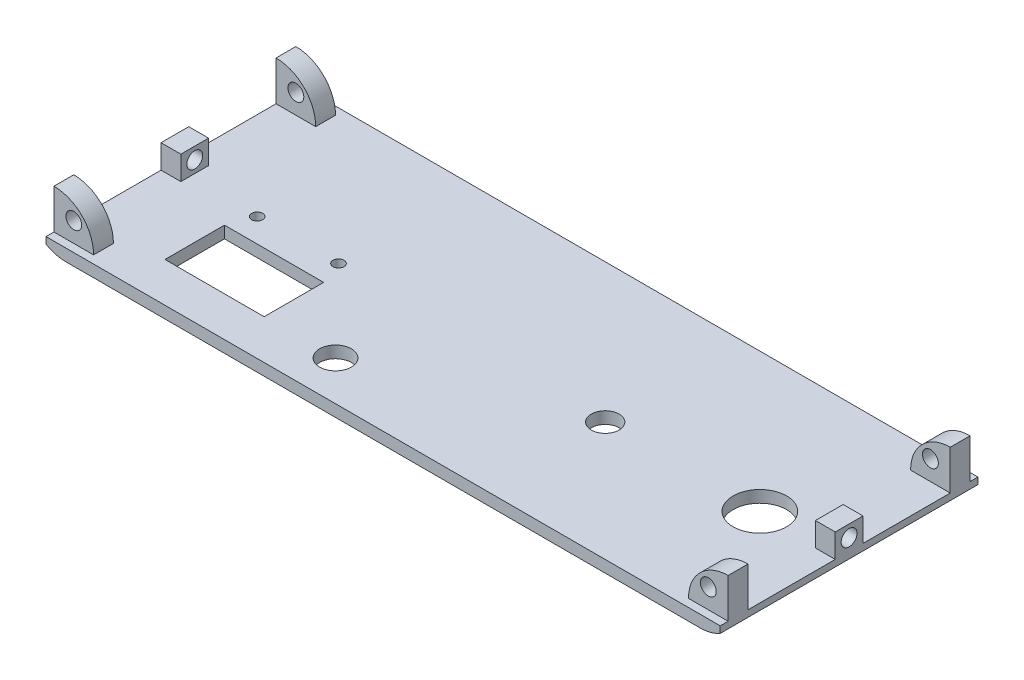
SolidWorks part; units mm, degrees
material "Allzweck-PBT"
ref_plane "Ebene vorne" through (0, 0, 0) normal (0, 0, 1) x (1, 0, 0)
ref_plane "Ebene oben" through (0, 0, 0) normal (0, 1, 0) x (1, 0, 0)
ref_plane "Ebene rechts" through (0, 0, 0) normal (1, 0, 0) x (0, 0, -1)
sketch "Skizze1" plane through (0, 0, 0) normal (0, 1, 0) x (1, 0, 0)
  line L1 (-90, 32.5) -> (90, 32.5)
  line L2 (-90, 32.5) -> (-90, -32.5)
  line L3 (-90, -32.5) -> (90, -32.5)
  line L4 (90, 32.5) -> (90, -32.5)
  line L5 (-90, 32.5) -> (90, -32.5) construction
  line L6 (-90, -32.5) -> (90, 32.5) construction
  point P0 (0, 0)
  dimension "D1" = 180
  dimension "D2" = 65
extrude "Aufsatz-Linear austragen1" add sketch "Skizze1" along normal blind 3
sketch "Skizze2" plane through (0, 0, 0) normal (0, -1, 0) x (-1, 0, 0)
  line L0 (90, 32.5) -> (90, -32.5) construction
  line L1 (65, -22.5) -> (40, -22.5)
  line L2 (65, -22.5) -> (65, -7.5)
  line L3 (65, -7.5) -> (40, -7.5)
  line L4 (40, -22.5) -> (40, -7.5)
  line L5 (65, -22.5) -> (40, -7.5) construction
  line L6 (65, -7.5) -> (40, -22.5) construction
  line L7 (-90, 32.5) -> (90, 32.5) construction
  point P0 (52.5, -15)
  dimension "D1" = 25
  dimension "D2" = 15
  dimension "D3" = 25
  dimension "D4" = 40
extrude "Schnitt-Linear austragen1" cut sketch "Skizze2" against normal blind 3
sketch "Skizze3" plane through (0, 3, 0) normal (0, 1, 0) x (1, 0, 0)
  line L0 (-90, 32.5) -> (-90, -32.5) construction
  line L1 (-85, 3.5) -> (-80, 3.5)
  line L2 (-85, 3.5) -> (-85, -3.5)
  line L3 (-85, -3.5) -> (-80, -3.5)
  line L4 (-80, 3.5) -> (-80, -3.5)
  line L5 (-85, 3.5) -> (-80, -3.5) construction
  line L6 (-85, -3.5) -> (-80, 3.5) construction
  line L7 (85, 3.5) -> (80, 3.5)
  line L8 (85, 3.5) -> (85, -3.5)
  line L9 (85, -3.5) -> (80, -3.5)
  line L10 (80, 3.5) -> (80, -3.5)
  line L11 (85, 3.5) -> (80, -3.5) construction
  line L12 (85, -3.5) -> (80, 3.5) construction
  line L13 (90, -32.5) -> (90, 32.5) construction
  line L14 (90, 32.5) -> (-90, 32.5) construction
  point P0 (-82.5, 0)
  point P5 (82.5, 0)
  point P10 (-85, 0)
  dimension "D1" = 5
  dimension "D2" = 5
  dimension "D3" = 5
  dimension "D4" = 7
  dimension "D5" = 5
  dimension "D6" = 7
  dimension "D7" = 32.5
  dimension "D8" = 32.5
extrude "Aufsatz-Linear austragen2" add sketch "Skizze3" along normal blind 6
sketch "Skizze4" plane through (0, 0, 32.5) normal (0, 0, 1) x (1, 0, 0)
  line L12 (-80, 0) -> (-90, 0)
  line L18 (-90, 0) -> (-90, 3)
  line L19 (-90, 3) -> (-85, 3)
  line L20 (-90, 3) -> (90, 3) construction
  line L21 (-85, 3) -> (-85, 1.3397)
  line L28 (80, 0) -> (90, 0)
  line L29 (90, 0) -> (90, 3)
  line L30 (90, 3) -> (85, 3)
  line L31 (85, 3) -> (85, 1.3397)
  arc A0 (-80, 0) -> (-85, 1.3397) centre (-80, 10) cw
  arc A1 (80, 0) -> (85, 1.3397) centre (80, 10) ccw
  point P6 (-90, 0)
  point P13 (90, 0)
  point P19 (90, 0)
  dimension "D1" = 10
  dimension "D2" = 10
  dimension "D4" = 1.3397
  dimension "D5" = 10
  dimension "D3" = 5
  dimension "D6" = 1.3397
  dimension "D7" = 10
hole_wizard "Ø4.0 (4) Durchmesser Bohrung1" positions "Skizze5" profile "Skizze6" hole size "Ø4.0" standard "DIN" end condition through all
sketch "Skizze5" plane through (-85, 0, 0) normal (-1, 0, 0) x (0, 0, 1)
  line L3 (-3.5, 9) -> (-3.5, 3) construction
  line L4 (-32.5, 3) -> (32.5, 3) construction
  point P0 (0, 6)
  dimension "D1" = 3
  dimension "D2" = 3.5
sketch "Skizze6" plane through (-85, 6, 0) normal (0, 1, 0) x (0, 0, 1)
  line L0 (0, 0) -> (0, 175)
  line L1 (0, 175) -> (2, 175)
  line L2 (2, 175) -> (2, 0)
  line L5 (2, 0) -> (0, 0)
  line L11 (0, -6.35) -> (0, 107.95) construction
  dimension "Bohrerdurchmesser" = 4
  dimension "Bohrungstiefe" = 175
extrude "Schnitt-Linear austragen4" cut sketch "Skizze4" against normal through all
sketch "Skizze7" plane through (0, 3, 0) normal (0, 1, 0) x (1, 0, 0)
  line L0 (-85, 32.5) -> (-85, 3.5) construction
  line L1 (-85, 30.5) -> (-75, 30.5)
  line L2 (-85, 30.5) -> (-85, 25.5)
  line L3 (-85, 25.5) -> (-75, 25.5)
  line L4 (-75, 30.5) -> (-75, 25.5)
  line L17 (85, 32.5) -> (-85, 32.5) construction
  dimension "D1" = 5
  dimension "D2" = 10
  dimension "D3" = 2
extrude "Aufsatz-Linear austragen3" add sketch "Skizze7" along normal blind 10
mirror "Spiegeln1" about plane through (0, 0, 0) normal (1, 0, 0) of "Aufsatz-Linear austragen3" second plane through (0, 0, 0) second plane normal (0, 0, 1)
fillet "Verrundung2" radius 10 20 edges at (-75, 8, -25.5) (-75, 8, -30.5) (-80, 13, -25.5) (-75, 13, -28) (-80, 13, -30.5) (-80, 13, 30.5) (-75, 13, 28) (-75, 8, 30.5) (-80, 13, 25.5) (-75, 8, 25.5) (80, 13, -30.5) (75, 13, -28) (75, 8, -30.5) (80, 13, -25.5) (75, 8, -25.5) (75, 8, 25.5) (75, 8, 30.5) (80, 13, 25.5) (75, 13, 28) (80, 13, 30.5)
hole_wizard "Ø4.0 (4) Durchmesser Bohrung3" positions "Skizze10" profile "Skizze11" hole size "Ø4.0" standard "DIN"
sketch "Skizze10" plane through (0, 0, -30.5) normal (0, 0, -1) x (-1, 0, 0)
  line L0 (-85, 13) -> (-85, 3) construction
  line L1 (-85, 3) -> (85, 3) construction
  line L2 (85, 13) -> (85, 3) construction
  line L4 (75, 3) -> (85, 3) construction
  point P0 (-80, 8)
  point P2 (80, 8)
  dimension "D1" = 5
  dimension "D2" = 5
  dimension "D3" = 5
  dimension "D4" = 5
sketch "Skizze11" plane through (80, 8, -30.5) normal (1, 0, 0) x (0, 1, 0)
  line L0 (0, 0) -> (0, 5)
  line L1 (0, 5) -> (2, 5)
  line L2 (2, 5) -> (2, 0)
  line L5 (2, 0) -> (0, 0)
  line L11 (0, -6.35) -> (0, 107.95) construction
  dimension "Bohrerdurchmesser" = 4
  dimension "Bohrungstiefe" = 5
hole_wizard "Ø4.0 (4) Durchmesser Bohrung4" positions "Skizze12" profile "Skizze13" hole size "Ø4.0" standard "DIN"
sketch "Skizze12" plane through (0, 0, 30.5) normal (0, 0, 1) x (1, 0, 0)
  line L0 (-85, 13) -> (-85, 3) construction
  line L3 (-85, 3) -> (85, 3) construction
  line L4 (75, 3) -> (85, 3) construction
  line L5 (85, 13) -> (85, 3) construction
  point P0 (-80, 8)
  point P2 (80, 8)
  dimension "D1" = 5
  dimension "D2" = 5
  dimension "D3" = 5
  dimension "D4" = 5
sketch "Skizze13" plane through (-80, 8, 30.5) normal (1, 0, 0) x (0, -1, 0)
  line L0 (0, 0) -> (0, 5)
  line L1 (0, 5) -> (2, 5)
  line L2 (2, 5) -> (2, 0)
  line L5 (2, 0) -> (0, 0)
  line L11 (0, -6.35) -> (0, 107.95) construction
  dimension "Bohrerdurchmesser" = 4
  dimension "Bohrungstiefe" = 5
sketch "Skizze14" plane through (0, 3, 0) normal (0, 1, 0) x (1, 0, 0)
  line L0 (100.2959, -2.5) -> (-139.8367, -2.5) construction
  line L2 (-85, -32.5) -> (85, -32.5) construction
  line L3 (-40, -7.5) -> (-40, -22.5) construction
  line L4 (-40, -7.5) -> (-40, -22.5) construction
  line L7 (-63.7023, -22.5) -> (1.0639, -22.5) construction
  line L8 (-40, -22.5) -> (-65, -22.5) construction
  circle A1 centre (26, -2.5) radius 3.5
  circle A2 centre (65, -2.5) radius 6.75
  circle A3 centre (-22, -22.5) radius 4
  dimension "D6" = 8
  dimension "D7" = 7
  dimension "D8" = 13.5
  dimension "D1" = 30
  dimension "D2" = 66
  dimension "D3" = 105
  dimension "D4" = 18
extrude "Schnitt-Linear austragen5" cut sketch "Skizze14" against normal through all
sketch "Skizze17" plane through (0, 3, 0) normal (0, 1, 0) x (1, 0, 0)
  line L2 (-65, -7.5) -> (-40, -7.5) construction
  line L6 (-65, -22.5) -> (-65, -7.5) construction
  circle A0 centre (-62.75, -1.5) radius 1.4
  circle A1 centre (-42.25, -1.5) radius 1.4
  dimension "D1" = 2.8
  dimension "D2" = 2.8
  dimension "D3" = 6
  dimension "D4" = 6
  dimension "D5" = 20.5
  dimension "D6" = 2.25
extrude "Schnitt-Linear austragen6" cut sketch "Skizze17" against normal blind 2
